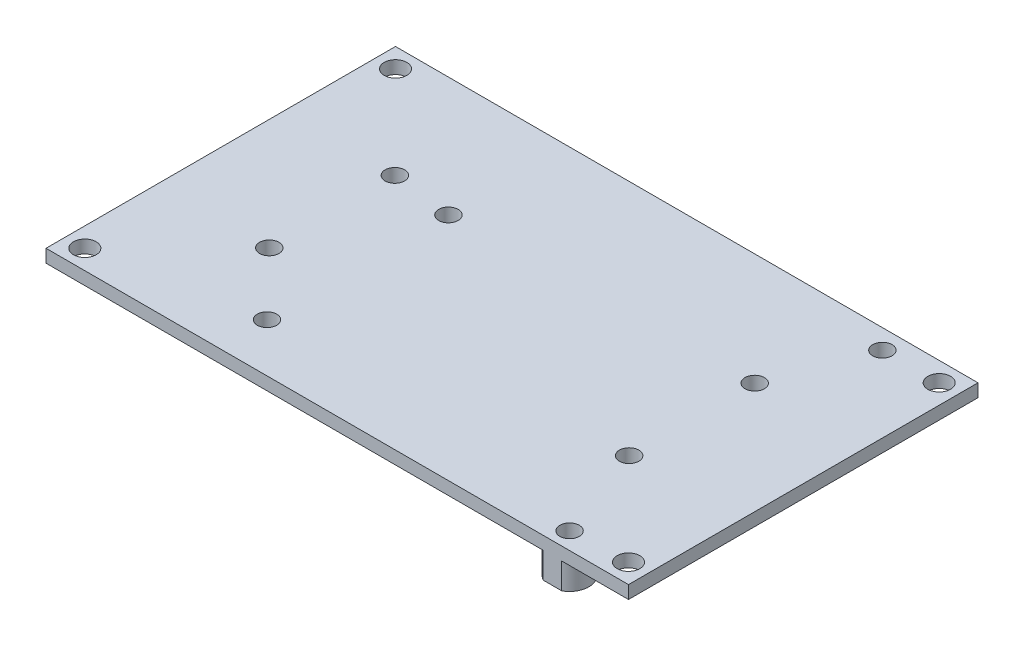
SolidWorks part; units mm, degrees
ref_plane "Front Plane" through (0, 0, 0) normal (0, 0, 1) x (1, 0, 0)
ref_plane "Top Plane" through (0, 0, 0) normal (0, 1, 0) x (1, 0, 0)
ref_plane "Right Plane" through (0, 0, 0) normal (1, 0, 0) x (0, 0, -1)
ref_plane "Plane1" through (0, 1, 0) normal (0, 1, 0) x (1, 0, 0)
sketch "Sketch2" plane through (0, 1, 0) normal (0, 1, 0) x (1, 0, 0)
  line L0 (-45, 0) -> (0, 0) construction
  line L5 (-45, -27) -> (0, -27)
  line L7 (-45, -24) -> (0, -24)
  line L10 (-45, 0) -> (0, 0)
  line L27 (0, 0) -> (0, -27)
  line L28 (-45, 0) -> (-45, -27)
  line L29 (-42, 0) -> (-42, -27)
  line L34 (0, 0) -> (0, -27) construction
  circle A1 centre (-27.8, -9.7) radius 1.5
  circle A5 centre (-27.8, -9.7) radius 3
  circle A10 centre (-42, -24) radius 1.75
  dimension "D17" = 6
  dimension "D22" = 3
  dimension "D3" = 9.7
  dimension "D4" = 17.2
  dimension "D5" = 3
  dimension "D6" = 27
  dimension "D7" = 45
  dimension "D8" = 3
extrude "Boss-Extrude1" add sketch "Sketch2" along normal blind 2 separate body contours A1 | L5 L27 L10 L28 | A10
sketch "Sketch5" plane through (0, 3, 0) normal (0, 1, 0) x (1, 0, 0)
  circle A0 centre (-27.8, -9.7) radius 3
  circle A1 centre (-27.8, -9.7) radius 1.5
extrude "Boss-Extrude2" add sketch "Sketch5" against normal blind 5
mirror "Mirror6" about plane through (0, 3, 0) normal (1, 0, 0) of bodies 117 114
mirror "Mirror7" about plane through (-45, 3, 0) normal (0, 0, -1) of bodies 115
sketch "Sketch8" plane through (0, 1, 0) normal (0, -1, 0) x (1, 0, 0)
  line L0 (31.8238, 27) -> (34.6857, 27)
  line L1 (-45, 27) -> (45, 27) construction
  circle A1 centre (33.2547, -23.9729) radius 1.5
  circle A3 centre (33.2547, 24.3633) radius 1.5
  circle A5 centre (-18.3708, -8.5472) radius 1.5
  circle A7 centre (-18.3708, 19.4848) radius 1.5
  circle A8 centre (-18.3708, -8.5472) radius 3
  circle A9 centre (-18.3708, 19.4848) radius 3
  circle A10 centre (33.2547, -23.9729) radius 3
  arc A11 (31.8238, 27) -> (34.6857, 27) centre (33.2547, 24.3633) ccw
extrude "Boss-Extrude3" add sketch "Sketch8" along normal blind 4 contours A9 | A8 | A10 | A11 L0 | A1 | A7 | A5 | A3
extrude "Cut-Extrude1" cut sketch "Sketch8<5>" against normal blind 4 contours A5 | A7 | A3 | A1 region at (-18.3708, 1, -8.5472) region at (-18.3708, 1, 19.4848)
sketch "Sketch8<5>" plane through (0, 1, 0) normal (0, -1, 0) x (1, 0, 0) same geometry as "Sketch8"
